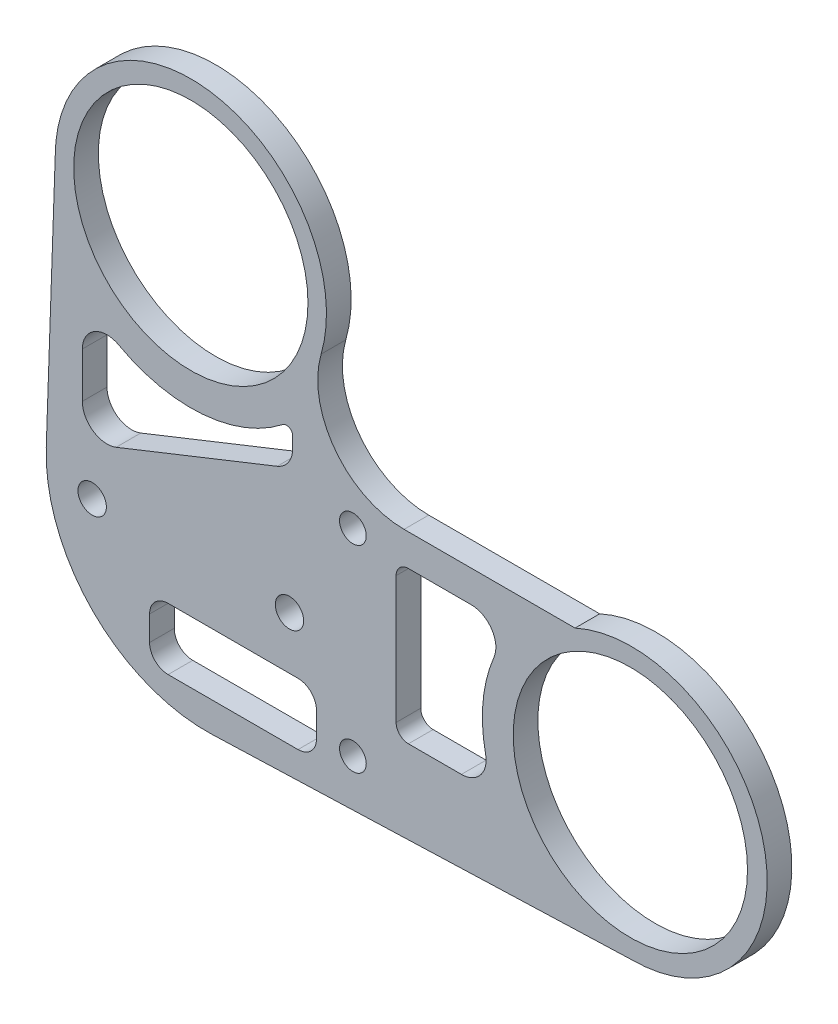
SolidWorks part; units mm, degrees
material "1.5918 (17CrNi6-6)"
ref_plane "前视基准面" through (0, 0, 0) normal (0, 0, 1) x (1, 0, 0)
ref_plane "上视基准面" through (0, 0, 0) normal (0, 1, 0) x (1, 0, 0)
ref_plane "右视基准面" through (0, 0, 0) normal (1, 0, 0) x (0, 0, -1)
sketch "草图3" plane through (0, 0, 0) normal (0, 0, 1) x (1, 0, 0)
  line L0 (-11, 0) -> (-11, -33)
  line L1 (35.74, -33) -> (-11, -33)
  line L2 (31.1574, -12) -> (9, -12)
  line L3 (9, -12) -> (9, -6.3246)
  arc A0 (9, -6.3246) -> (-11, 0) centre (0, 0) ccw
  arc A1 (35.74, -33) -> (31.1574, -12) centre (35.74, -22) ccw
  circle A2 centre (0, 0) radius 9.5
  circle A3 centre (35.74, -22) radius 9.5
  dimension "D1" = 35.74
  dimension "D2" = 22
  dimension "D4" = 19
  dimension "D3" = 22
  dimension "D5" = 10
  dimension "D6" = 9
extrude "凸台-拉伸1" add sketch "草图3" along normal blind 2
sketch "草图4" plane through (0, 0, 2) normal (0, 0, 1) x (1, 0, 0)
  line L0 (35.74, -33) -> (-12.2109, -34.6745)
  line L1 (-12.2109, -34.6745) -> (-11, 0)
  line L2 (-11, -33) -> (35.74, -33) construction
  line L3 (-11, 0) -> (-11, -33) construction
  line L8 (-11, 0) -> (-11, -33)
  line L9 (-11, -33) -> (35.74, -33)
  line L10 (31.1574, -12) -> (9, -12)
  line L11 (9, -12) -> (9, -6.3246)
  line L14 (31.1574, -12) -> (9, -12)
  line L15 (9, -12) -> (9, -6.3246)
  arc A2 (9, -6.3246) -> (-11, 0) centre (0, 0) ccw
  arc A3 (35.74, -33) -> (31.1574, -12) centre (35.74, -22) ccw
  arc A4 (9, -6.3246) -> (-11, 0) centre (0, 0) ccw
  arc A5 (35.74, -33) -> (31.1574, -12) centre (35.74, -22) ccw
  dimension "D1" = 2
  dimension "D2" = 2
  dimension "D3" = 0
extrude "凸台-拉伸2" add sketch "草图4" against normal blind 2
fillet "圆角2" radius 13 1 edges at (-12.2109, -34.6745, 1)
sketch "草图5" plane through (0, 0, 2) normal (0, 0, 1) x (1, 0, 0)
  line L0 (0, 0) -> (0, -6.5656) construction
  circle A0 centre (-8, -22.5) radius 1.15
  circle A1 centre (8, -22.5) radius 1.15
  dimension "D3" = 2.3
  dimension "D4" = 8
  dimension "D1" = 16
  dimension "D2" = 22.5
extrude "切除-拉伸1" cut sketch "草图5" against normal through all
sketch "草图6" plane through (0, 0, 2) normal (0, 0, 1) x (1, 0, 0)
  circle A0 centre (0, 0) radius 9.5
  circle A2 centre (35.6428, -22) radius 9.5
  dimension "D1" = 19
extrude "切除-拉伸2" cut sketch "草图6" against normal through all
fillet "圆角3" radius 8 1 edges at (9, -12, 1)
fillet "圆角4" radius 7 1 edges at (9, -6.3246, 1)
sketch "草图7" plane through (0, 0, 2) normal (0, 0, 1) x (1, 0, 0)
  line L0 (45.1428, -22) -> (2.3972, -22) construction
  circle A0 centre (35.6428, -22) radius 9.5 construction
  circle A1 centre (13.1428, -14) radius 1.0833
  circle A2 centre (13.1428, -30) radius 1.0833
  dimension "D1" = 22.5
  dimension "D2" = 8
extrude "切除-拉伸4" cut sketch "草图7" against normal blind 10
sketch "草图8" plane through (0, 0, 2) normal (0, 0, 1) x (1, 0, 0)
  line L0 (16.6465, -26.8838) -> (16.6465, -14.5726)
  line L1 (-1.8442, -26.7629) -> (8.6913, -26.7629)
  line L2 (-3.3442, -28.2629) -> (-3.3442, -30.2665)
  line L3 (-1.8442, -31.7665) -> (8.6913, -31.7665)
  line L4 (10.1913, -28.2629) -> (10.1913, -30.2665)
  line L5 (16.6465, -14.5726) -> (22.7377, -14.5726)
  line L6 (16.6465, -26.8838) -> (21.943, -26.8838)
  line L7 (-8.7969, -16.0529) -> (-8.7969, -12.3803)
  line L9 (-6.0577, -17.9113) -> (6.9986, -12.7179)
  line L10 (8.2594, -10.8596) -> (8.2594, -9.957)
  arc A3 (-5.8344, -10.6271) -> (7.452, -9.5626) centre (0, 0) ccw
  arc A5 (-8.7969, -12.3803) -> (-5.8344, -10.6271) centre (-6.7969, -12.3803) cw
  arc A6 (8.2594, -10.8596) -> (6.9986, -12.7179) centre (6.2594, -10.8596) cw
  arc A7 (-8.7969, -16.0529) -> (-6.0577, -17.9113) centre (-6.7969, -16.0529) ccw
  arc A8 (8.2594, -9.957) -> (7.452, -9.5626) centre (7.7594, -9.957) ccw
  arc A11 (-3.3442, -30.2665) -> (-1.8442, -31.7665) centre (-1.8442, -30.2665) ccw
  arc A12 (-3.3442, -28.2629) -> (-1.8442, -26.7629) centre (-1.8442, -28.2629) cw
  arc A13 (10.1913, -30.2665) -> (8.6913, -31.7665) centre (8.6913, -30.2665) cw
  arc A14 (10.1913, -28.2629) -> (8.6913, -26.7629) centre (8.6913, -28.2629) ccw
  arc A15 (24.5813, -17.3479) -> (23.9002, -24.4718) centre (35.6428, -22) ccw
  arc A16 (21.943, -26.8838) -> (23.9002, -24.4718) centre (21.943, -24.8838) ccw
  arc A17 (24.5813, -17.3479) -> (22.7377, -14.5726) centre (22.7377, -16.5726) ccw
  point P7 (28.0321, -13.3787)
  point P13 (25.8241, -27.9868)
  point P21 (8.2594, -12.2164)
  dimension "D1" = 2
  dimension "D2" = 2
  dimension "D3" = 0.5
  dimension "D4" = 2
  dimension "D5" = 1.5
  dimension "D6" = 24
extrude "切除-拉伸5" cut sketch "草图8" against normal blind 10
fillet "圆角5" radius 1 2 edges at (16.6465, -26.8838, 1) (16.6465, -14.5726, 1)
